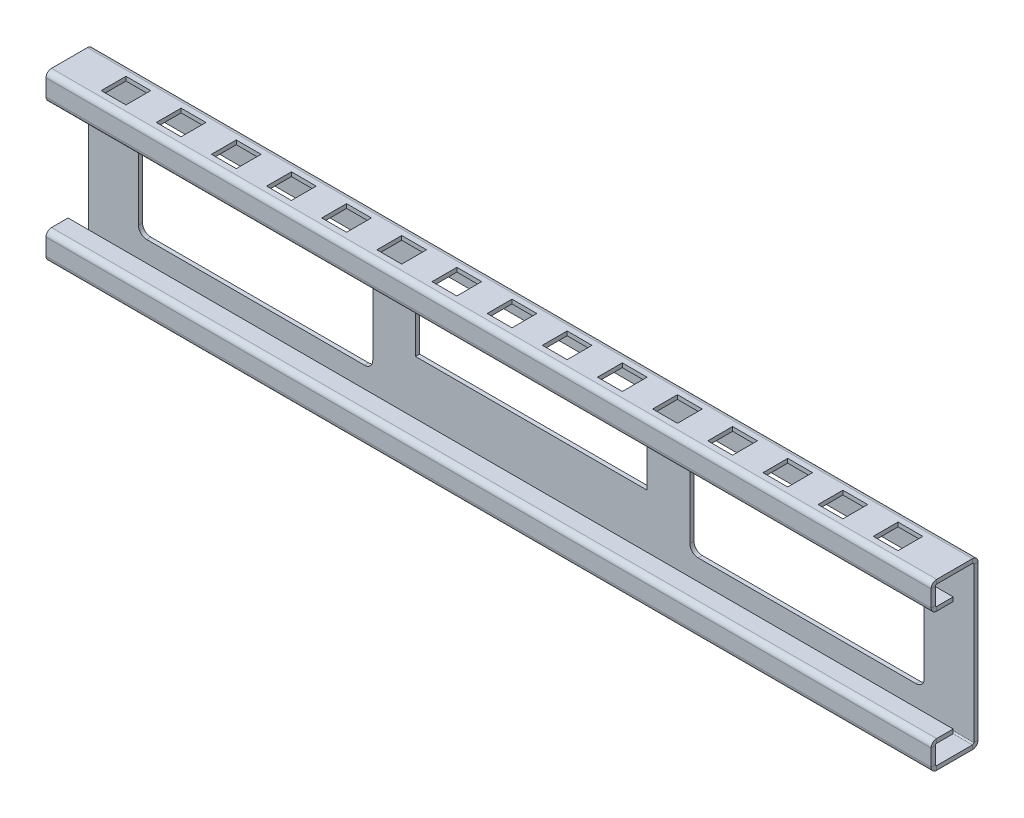
SolidWorks part; units mm, degrees
note: The reader was unsure of these and kept them because the rebuilt part matched: thickness of "基体-法兰1", "边线-法兰1", "边线-法兰2", "边线-法兰3", "钣金6", "钣金7", "钣金8", "钣金9", "钣金13", "钣金16", "钣金17", "钣金18", "钣金19", "钣金20"; flange length of "边线-法兰1", "边线-法兰2", "边线-法兰3".
material "普通碳钢"
ref_plane "前视基准面" through (0, 0, 0) normal (0, 0, 1) x (1, 0, 0)
ref_plane "上视基准面" through (0, 0, 0) normal (0, 1, 0) x (1, 0, 0)
ref_plane "右视基准面" through (0, 0, 0) normal (1, 0, 0) x (0, 0, -1)
sketch "草图1" plane through (0, 0, 0) normal (0, 0, 1) x (1, 0, 0)
  line L1 (-160.5, 30) -> (160.5, 30)
  line L2 (-160.5, 30) -> (-160.5, -30)
  line L3 (-160.5, -30) -> (160.5, -30)
  line L4 (160.5, 30) -> (160.5, -30)
  line L5 (-160.5, 30) -> (160.5, -30) construction
  line L6 (-160.5, -30) -> (160.5, 30) construction
  point P0 (0, 0)
  dimension "D1" = 321
  dimension "D2" = 60
base flange "基体-法兰1" sketch "草图1" thickness 1.5 reverse thickness direction no parameters "D1"=0.5
edge flange "边线-法兰1" sketch "草图10" flange profiles "草图10", "草图11" flange angle 90 flange length 17 flange position material inside bend radius 0.5 thickness 1.5 parameters "D1"=1, "D6"=10, "D8"=1
sketch "草图10" plane through (0, 30, 0) normal (0, 1, 0) x (-1, 0, 0)
  line L2 (-160.5, 0) -> (-160.5, 15.5)
  line L3 (-160.5, 15.5) -> (160.5, 15.5)
  line L4 (160.5, 15.5) -> (160.5, 0)
  line L5 (-160.5, 0) -> (160.5, 0) construction
  line L6 (-160.5, 0) -> (160.5, 0)
sketch "草图11" plane through (0, -30, 0) normal (0, -1, 0) x (1, 0, 0)
  line L0 (-160.5, 0) -> (160.5, 0) construction
  line L1 (-160.5, 0) -> (160.5, 0)
  line L2 (-160.5, 0) -> (-160.5, 15.5)
  line L3 (-160.5, 15.5) -> (160.5, 15.5)
  line L4 (160.5, 15.5) -> (160.5, 0)
bend "边线折弯1" bend radius 0.5 bend angle 90 parameters "D5"=1
bend "边线折弯2" bend radius 0.5 bend angle 90 parameters "D5"=2
edge flange "边线-法兰2" sketch "草图16" flange profiles "草图16", "草图17" flange angle 90 flange length 10 flange position material inside bend radius 0.5 thickness 1.5 parameters "D1"=1, "D6"=10, "D8"=1
sketch "草图16" plane through (0, 28.5, 15.5) normal (0, 0, -1) x (1, 0, 0)
  line L1 (160.5, 0) -> (-160.5, 0) construction
  line L2 (-160.5, 0) -> (-160.5, 8.5)
  line L3 (-160.5, 8.5) -> (160.5, 8.5)
  line L4 (160.5, 8.5) -> (160.5, 0)
  line L5 (160.5, 0) -> (-160.5, 0)
sketch "草图17" plane through (0, -28.5, 15.5) normal (0, 0, -1) x (-1, 0, 0)
  line L0 (160.5, 0) -> (-160.5, 0) construction
  line L1 (160.5, 0) -> (-160.5, 0)
  line L2 (160.5, 0) -> (160.5, 8.5)
  line L3 (160.5, 8.5) -> (-160.5, 8.5)
  line L4 (-160.5, 8.5) -> (-160.5, 0)
bend "边线折弯3" bend radius 0.5 bend angle 90 parameters "D5"=3
bend "边线折弯4" bend radius 0.5 bend angle 90 parameters "D5"=4
sketch "草图18" plane through (0, 0, -1.5) normal (0, 0, -1) x (-1, 0, 0)
  line L0 (35.0448, 0) -> (17.959, 0) construction
  line L1 (-39.5, 20) -> (39.5, 20)
  line L2 (-42.5, 17) -> (-42.5, -17)
  line L3 (-39.5, -20) -> (39.5, -20)
  line L4 (42.5, 17) -> (42.5, -17)
  line L5 (-42.5, 20) -> (42.5, -20) construction
  line L6 (-42.5, -20) -> (42.5, 20) construction
  line L7 (160.5, 30) -> (-160.5, 30) construction
  arc A0 (39.5, 20) -> (42.5, 17) centre (39.5, 17) cw
  arc A1 (42.5, -17) -> (39.5, -20) centre (39.5, -17) cw
  arc A2 (-39.5, -20) -> (-42.5, -17) centre (-39.5, -17) cw
  arc A3 (-42.5, 17) -> (-39.5, 20) centre (-39.5, 17) cw
  point P0 (0, 0)
  dimension "D4" = 3
  dimension "D1" = 85
  dimension "D2" = 10
  dimension "D3" = 0
extrude "切除-拉伸1" cut sketch "草图18" against normal blind 10
pattern_linear "阵列(线性)1" count 2 spacing 100 along (-1, 0, 0) count 2 spacing 100 along (1, 0, 0) of "切除-拉伸1"
sketch "草图19" plane through (0, 30, 0) normal (0, 1, 0) x (1, 0, 0)
  line L0 (0, 36.0868) -> (0, -45.539) construction
  line L6 (-160.5, 1.5) -> (160.5, 1.5) construction
  line L7 (-4.5, -2.5) -> (4.5, -2.5)
  line L8 (-4.5, -2.5) -> (-4.5, -11.5)
  line L9 (-4.5, -11.5) -> (4.5, -11.5)
  line L10 (4.5, -2.5) -> (4.5, -11.5)
  line L11 (-4.5, -2.5) -> (4.5, -11.5) construction
  line L12 (-4.5, -11.5) -> (4.5, -2.5) construction
  point P3 (0, -7)
  dimension "D1" = 9
  dimension "D2" = 9
  dimension "D3" = 8.5
extrude "切除-拉伸2" cut sketch "草图19" against normal through all normal cut yes
pattern_linear "阵列(线性)2" count 8 spacing 20 along (-1, 0, 0) count 8 spacing 20 along (1, 0, 0) of "切除-拉伸2"
edge flange "边线-法兰3" sketch "草图24" flange profiles "草图24", "草图25" flange angle 90 flange length 8 flange position material inside bend radius 0.5 thickness 1.5 parameters "D6"=10, "D8"=0.5
sketch "草图24" plane through (0, -20, 14) normal (0, 1, 0) x (1, 0, 0)
  line L0 (-160.5, 0) -> (160.5, 0) construction
  line L1 (-160.5, 0) -> (160.5, 0)
  line L2 (-160.5, 0) -> (-160.5, 6.5)
  line L3 (-160.5, 6.5) -> (160.5, 6.5)
  line L4 (160.5, 6.5) -> (160.5, 0)
sketch "草图25" plane through (0, 20, 14) normal (0, -1, 0) x (-1, 0, 0)
  line L0 (-160.5, 0) -> (160.5, 0) construction
  line L1 (-160.5, 0) -> (160.5, 0)
  line L2 (-160.5, 0) -> (-160.5, 6.5)
  line L3 (-160.5, 6.5) -> (160.5, 6.5)
  line L4 (160.5, 6.5) -> (160.5, 0)
bend "边线折弯5" bend radius 0.5 bend angle 90 parameters "D5"=5
bend "边线折弯6" bend radius 0.5 bend angle 90 parameters "D5"=6
sketch "草图26" plane through (0, 0, -1.5) normal (0, 0, -1) x (-1, 0, 0)
  line L0 (0, 0) -> (0, 73.9374) construction
  line L1 (42.5, -17) -> (42.5, 17) construction
  line L2 (-39.5, -20) -> (39.5, -20) construction
  line L3 (-42.5, 17) -> (-42.5, -17) construction
  line L4 (39.5, 20) -> (-39.5, 20) construction
  line L5 (42.5, -17) -> (42.5, 17)
  line L6 (-39.5, -20) -> (39.5, -20)
  line L7 (-42.5, 17) -> (-42.5, -17)
  line L8 (39.5, 20) -> (-39.5, 20)
  arc A0 (42.5, 17) -> (39.5, 20) centre (39.5, 17) ccw construction
  arc A1 (39.5, -20) -> (42.5, -17) centre (39.5, -17) ccw construction
  arc A2 (-42.5, -17) -> (-39.5, -20) centre (-39.5, -17) ccw construction
  arc A3 (-39.5, 20) -> (-42.5, 17) centre (-39.5, 17) ccw construction
  arc A4 (42.5, 17) -> (39.5, 20) centre (39.5, 17) ccw
  arc A5 (39.5, -20) -> (42.5, -17) centre (39.5, -17) ccw
  arc A6 (-42.5, -17) -> (-39.5, -20) centre (-39.5, -17) ccw
  arc A7 (-39.5, 20) -> (-42.5, 17) centre (-39.5, 17) ccw
extrude "凸台-拉伸1" add sketch "草图26" against normal up to surface (1.5 mm away) up to face at (-100, 0, 0)
sketch "草图27" plane through (0, 0, -1.5) normal (0, 0, -1) x (-1, 0, 0)
  line L0 (0, 0) -> (0, 73.2698) construction
  line L1 (0, 0) -> (90.1268, 0) construction
  line L6 (-42, 23) -> (42, 23)
  line L7 (-42, 23) -> (-42, -8)
  line L8 (-42, -8) -> (42, -8)
  line L9 (42, 23) -> (42, -8)
  line L10 (-42, 23) -> (42, -8) construction
  line L11 (-42, -8) -> (42, 23) construction
  point P3 (0, 7.5)
  dimension "D1" = 84
  dimension "D2" = 31
  dimension "D3" = 8
extrude "切除-拉伸3" cut sketch "草图27" against normal blind 6 normal cut yes
sketch "折弯-线1" [suppressed] plane through (0, 0, 0) normal (0, 1, 0) x (-1, 0, 0)
sketch "边界框1" [suppressed] plane through (0, 0, 0) normal (0, 1, 0) x (-1, 0, 0)
sheet metal parameters "钣金6" thickness 1.5 parameters "D1"=0.5, "D7"=1
flat pattern "平板型式6" [suppressed]
sketch "折弯-线2" plane through (0, 0, 0) normal (0, 1, 0) x (-1, 0, 0)
sketch "边界框2" [suppressed] plane through (0, 0, 0) normal (0, 1, 0) x (-1, 0, 0)
sheet metal parameters "钣金7" thickness 1.5 parameters "D1"=0.5, "D7"=1
flat pattern "平板型式6" [suppressed]
sketch "折弯-线2" plane through (0, 0, 0) normal (0, 1, 0) x (-1, 0, 0)
sketch "边界框2" [suppressed] plane through (0, 0, 0) normal (0, 1, 0) x (-1, 0, 0)
bend of the flat pattern "展开-<边线折弯1>1"
bend of the flat pattern "展开-<边线折弯2>1"
sheet metal parameters "钣金8" thickness 1.5 parameters "D1"=0.5, "D7"=1
flat pattern "平板型式6" [suppressed]
sketch "折弯-线2" plane through (0, 0, 0) normal (0, 1, 0) x (-1, 0, 0)
sketch "边界框2" [suppressed] plane through (0, 0, 0) normal (0, 1, 0) x (-1, 0, 0)
bend of the flat pattern "展开-<边线折弯1>1"
bend of the flat pattern "展开-<边线折弯2>1"
bend of the flat pattern "展开-<边线折弯3>1"
bend of the flat pattern "展开-<边线折弯4>1"
sheet metal parameters "钣金9" thickness 1.5 parameters "D1"=0.5, "D7"=1
flat pattern "平板型式6" [suppressed]
sketch "折弯-线2" plane through (0, 0, 0) normal (0, 1, 0) x (-1, 0, 0)
sketch "边界框2" [suppressed] plane through (0, 0, 0) normal (0, 1, 0) x (-1, 0, 0)
bend of the flat pattern "展开-<边线折弯1>1"
bend of the flat pattern "展开-<边线折弯2>1"
bend of the flat pattern "展开-<边线折弯3>1"
bend of the flat pattern "展开-<边线折弯4>1"
sheet metal parameters "钣金13" thickness 1.5 parameters "D1"=0.5, "D7"=1
flat pattern "平板型式6"
sketch "折弯-线2" plane through (0, 0, 0) normal (0, 0, 1) x (1, 0, 0)
  line L0 (-168, -55.45) -> (168, -55.45) construction
  line L1 (168, 55.45) -> (-168, 55.45) construction
  line L2 (-168, -29.15) -> (168, -29.15) construction
  line L3 (168, 29.15) -> (-168, 29.15) construction
  line L4 (-168, -55.45) -> (168, -55.45) construction
  line L5 (168, 55.45) -> (-168, 55.45) construction
  line L6 (-168, -29.15) -> (168, -29.15) construction
  line L7 (168, 29.15) -> (-168, 29.15) construction
sketch3d "边界框2" [suppressed]
  line L0 (-168, -64.6, 0) -> (168, -64.6, 0) construction
  line L1 (-168, 64.6, 0) -> (168, 64.6, 0) construction
  line L2 (-168, -64.6, 0) -> (-168, 64.6, 0) construction
  line L3 (168, -64.6, 0) -> (168, 64.6, 0) construction
bend of the flat pattern "展开-<边线折弯1>1"
bend of the flat pattern "展开-<边线折弯2>1"
bend of the flat pattern "展开-<边线折弯3>1"
bend of the flat pattern "展开-<边线折弯4>1"
sheet metal parameters "钣金16" thickness 1.5 parameters "D1"=0.5, "D7"=1
flat pattern "平板型式6"
sketch "折弯-线2" plane through (0, 0, 0) normal (0, 0, 1) x (1, 0, 0)
  line L0 (-168, -55.45) -> (168, -55.45) construction
  line L1 (168, 55.45) -> (-168, 55.45) construction
  line L2 (-168, -29.15) -> (168, -29.15) construction
  line L3 (168, 29.15) -> (-168, 29.15) construction
  line L4 (-168, -55.45) -> (168, -55.45) construction
  line L5 (168, 55.45) -> (-168, 55.45) construction
  line L6 (-168, -29.15) -> (168, -29.15) construction
  line L7 (168, 29.15) -> (-168, 29.15) construction
sketch3d "边界框2" [suppressed]
  line L0 (-168, -64.6, 0) -> (168, -64.6, 0) construction
  line L1 (-168, 64.6, 0) -> (168, 64.6, 0) construction
  line L2 (-168, -64.6, 0) -> (-168, 64.6, 0) construction
  line L3 (168, -64.6, 0) -> (168, 64.6, 0) construction
bend of the flat pattern "展开-<边线折弯1>1"
bend of the flat pattern "展开-<边线折弯2>1"
bend of the flat pattern "展开-<边线折弯3>1"
bend of the flat pattern "展开-<边线折弯4>1"
sheet metal parameters "钣金17" thickness 1.5 parameters "D1"=0.5, "D7"=1
flat pattern "平板型式6"
sketch "折弯-线2" plane through (0, 0, 0) normal (0, 0, 1) x (1, 0, 0)
  line L0 (-168, -55.45) -> (168, -55.45) construction
  line L1 (168, 55.45) -> (-168, 55.45) construction
  line L2 (-168, -29.15) -> (168, -29.15) construction
  line L3 (168, 29.15) -> (-168, 29.15) construction
  line L4 (-168, -55.45) -> (168, -55.45) construction
  line L5 (168, 55.45) -> (-168, 55.45) construction
  line L6 (-168, -29.15) -> (168, -29.15) construction
  line L7 (168, 29.15) -> (-168, 29.15) construction
sketch3d "边界框2" [suppressed]
  line L0 (-168, -64.6, 0) -> (168, -64.6, 0) construction
  line L1 (-168, 64.6, 0) -> (168, 64.6, 0) construction
  line L2 (-168, -64.6, 0) -> (-168, 64.6, 0) construction
  line L3 (168, -64.6, 0) -> (168, 64.6, 0) construction
bend of the flat pattern "展开-<边线折弯1>1"
bend of the flat pattern "展开-<边线折弯2>1"
bend of the flat pattern "展开-<边线折弯3>1"
bend of the flat pattern "展开-<边线折弯4>1"
sheet metal parameters "钣金18" thickness 1.5 parameters "D1"=0.5, "D7"=1
flat pattern "平板型式6" [suppressed]
sketch "折弯-线2" plane through (0, 0, 0) normal (0, 0, 1) x (1, 0, 0)
  line L0 (-168, -55.45) -> (168, -55.45) construction
  line L1 (168, 55.45) -> (-168, 55.45) construction
  line L2 (-168, -29.15) -> (168, -29.15) construction
  line L3 (168, 29.15) -> (-168, 29.15) construction
  line L4 (-168, -55.45) -> (168, -55.45) construction
  line L5 (168, 55.45) -> (-168, 55.45) construction
  line L6 (-168, -29.15) -> (168, -29.15) construction
  line L7 (168, 29.15) -> (-168, 29.15) construction
sketch3d "边界框2" [suppressed]
  line L0 (-168, -64.6, 0) -> (168, -64.6, 0) construction
  line L1 (-168, 64.6, 0) -> (168, 64.6, 0) construction
  line L2 (-168, -64.6, 0) -> (-168, 64.6, 0) construction
  line L3 (168, -64.6, 0) -> (168, 64.6, 0) construction
bend of the flat pattern "展开-<边线折弯1>1"
bend of the flat pattern "展开-<边线折弯2>1"
bend of the flat pattern "展开-<边线折弯3>1"
bend of the flat pattern "展开-<边线折弯4>1"
bend of the flat pattern "展开-<边线折弯5>1"
bend of the flat pattern "展开-<边线折弯6>1"
sheet metal parameters "钣金19" thickness 1.5 parameters "D1"=0.5, "D7"=1
flat pattern "平板型式6" [suppressed]
sketch "折弯-线2" plane through (0, 0, 0) normal (0, 0, 1) x (1, 0, 0)
  line L0 (-168, -55.45) -> (168, -55.45) construction
  line L1 (168, 55.45) -> (-168, 55.45) construction
  line L2 (-168, -29.15) -> (168, -29.15) construction
  line L3 (168, 29.15) -> (-168, 29.15) construction
  line L4 (-168, -55.45) -> (168, -55.45) construction
  line L5 (168, 55.45) -> (-168, 55.45) construction
  line L6 (-168, -29.15) -> (168, -29.15) construction
  line L7 (168, 29.15) -> (-168, 29.15) construction
sketch3d "边界框2" [suppressed]
  line L0 (-168, -64.6, 0) -> (168, -64.6, 0) construction
  line L1 (-168, 64.6, 0) -> (168, 64.6, 0) construction
  line L2 (-168, -64.6, 0) -> (-168, 64.6, 0) construction
  line L3 (168, -64.6, 0) -> (168, 64.6, 0) construction
bend of the flat pattern "展开-<边线折弯1>1"
bend of the flat pattern "展开-<边线折弯2>1"
bend of the flat pattern "展开-<边线折弯3>1"
bend of the flat pattern "展开-<边线折弯4>1"
bend of the flat pattern "展开-<边线折弯5>1"
bend of the flat pattern "展开-<边线折弯6>1"
sheet metal parameters "钣金20" thickness 1.5 parameters "D1"=0.5, "D7"=1
flat pattern "平板型式6" [suppressed]
sketch "折弯-线2" plane through (0, 0, 0) normal (0, 0, 1) x (1, 0, 0)
  line L0 (-168, -55.45) -> (168, -55.45) construction
  line L1 (168, 55.45) -> (-168, 55.45) construction
  line L2 (-168, -29.15) -> (168, -29.15) construction
  line L3 (168, 29.15) -> (-168, 29.15) construction
  line L4 (-168, -55.45) -> (168, -55.45) construction
  line L5 (168, 55.45) -> (-168, 55.45) construction
  line L6 (-168, -29.15) -> (168, -29.15) construction
  line L7 (168, 29.15) -> (-168, 29.15) construction
sketch3d "边界框2" [suppressed]
  line L0 (-168, -64.6, 0) -> (168, -64.6, 0) construction
  line L1 (-168, 64.6, 0) -> (168, 64.6, 0) construction
  line L2 (-168, -64.6, 0) -> (-168, 64.6, 0) construction
  line L3 (168, -64.6, 0) -> (168, 64.6, 0) construction
bend of the flat pattern "展开-<边线折弯1>1"
bend of the flat pattern "展开-<边线折弯2>1"
bend of the flat pattern "展开-<边线折弯3>1"
bend of the flat pattern "展开-<边线折弯4>1"
bend of the flat pattern "展开-<边线折弯5>1"
bend of the flat pattern "展开-<边线折弯6>1"
